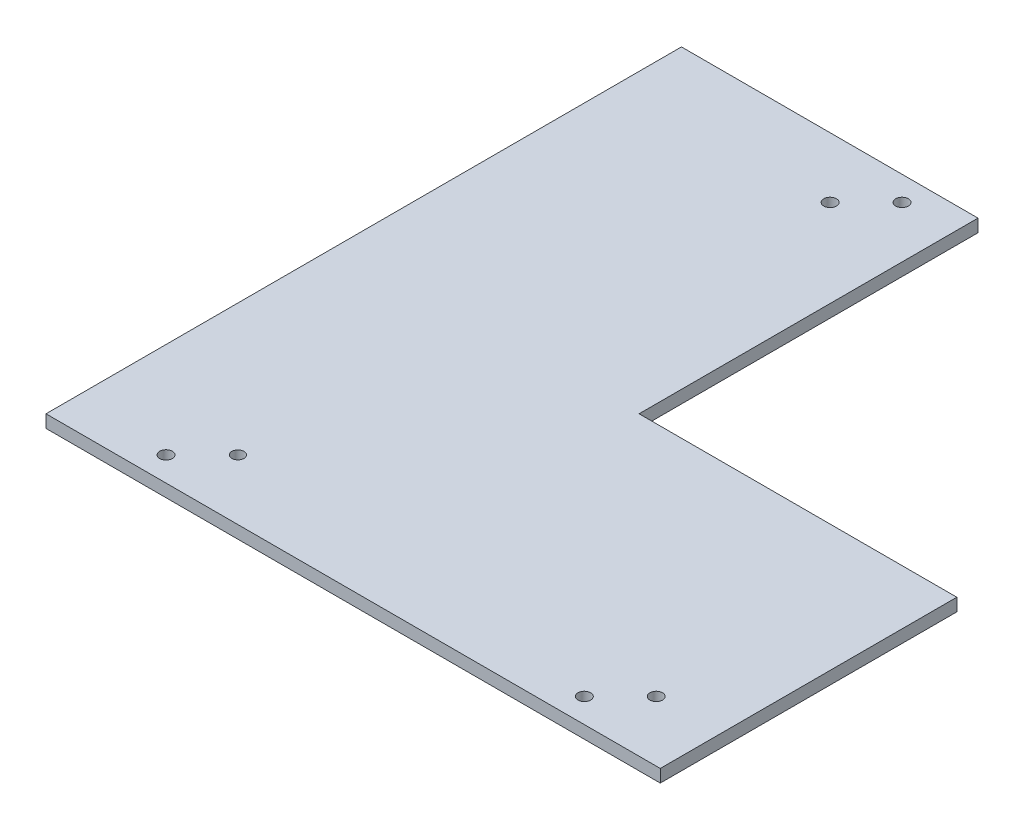
SolidWorks part; units mm, degrees
ref_plane "Front Plane" through (0, 0, 0) normal (0, 0, 1) x (1, 0, 0)
ref_plane "Top Plane" through (0, 0, 0) normal (0, 1, 0) x (1, 0, 0)
ref_plane "Right Plane" through (0, 0, 0) normal (1, 0, 0) x (0, 0, -1)
sketch "Sketch1" plane through (0, 0, 0) normal (0, 1, 0) x (1, 0, 0)
  line L0 (-72.5, -35) -> (72.5, -35)
  line L2 (-72.5, -35) -> (-72.5, 35)
  line L4 (72.5, -35) -> (72.5, 35)
  line L5 (-72.5, -35) -> (72.5, 35) construction
  line L6 (-72.5, 35) -> (72.5, -35) construction
  line L15 (-2.5, 35) -> (72.5, 35)
  line L17 (-72.5, 35) -> (-72.5, 115)
  line L18 (-72.5, 115) -> (-2.5, 115)
  line L19 (-2.5, 35) -> (-2.5, 115)
  circle A0 centre (-49.9264, -29.2426) radius 1.5
  circle A1 centre (-41.4411, -20.7574) radius 1.4446
  circle A2 centre (48.8155, -29.2426) radius 1.5
  circle A3 centre (57.3007, -20.7574) radius 1.5
  circle A4 centre (-23.1636, 100.7574) radius 1.5
  circle A5 centre (-14.6783, 109.2426) radius 1.5
  point P0 (0, 0)
  dimension "D1" = 145
  dimension "D2" = 70
  dimension "D3" = 70
  dimension "D4" = 150
extrude "Boss-Extrude1" add sketch "Sketch1" along normal blind 3
